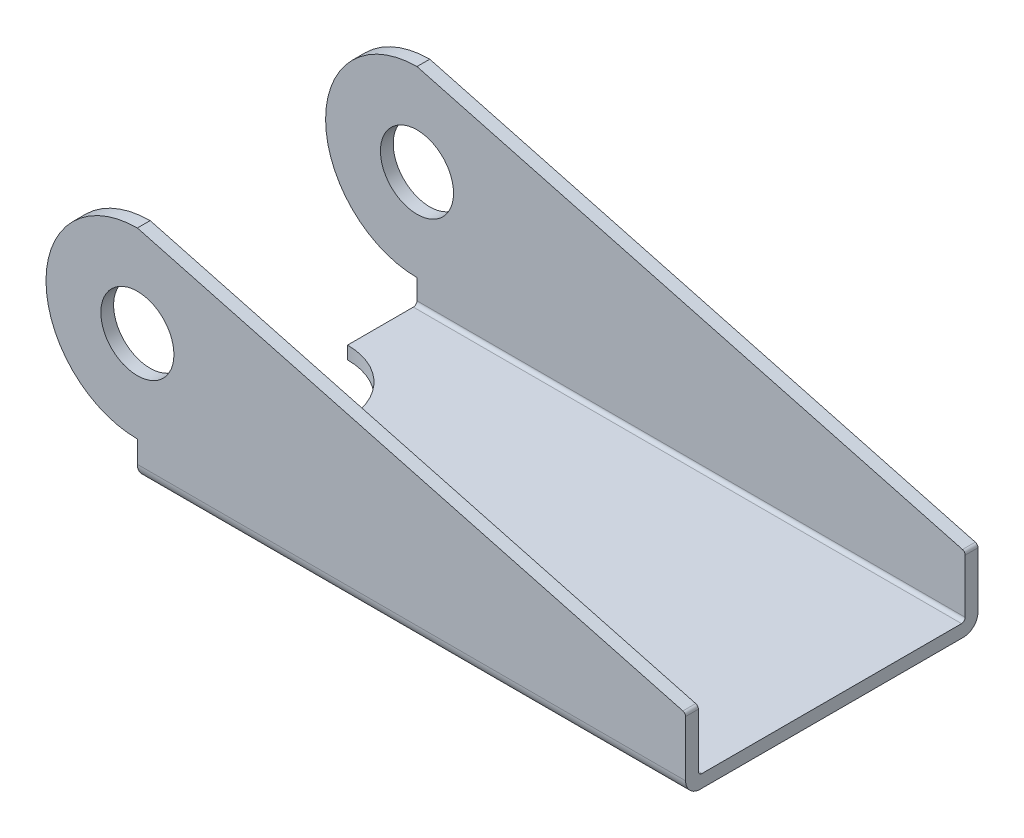
SolidWorks part; units mm, degrees
ref_plane "Front Plane" through (0, 0, 0) normal (0, 0, 1) x (1, 0, 0)
ref_plane "Top Plane" through (0, 0, 0) normal (0, 1, 0) x (1, 0, 0)
ref_plane "Right Plane" through (0, 0, 0) normal (1, 0, 0) x (0, 0, -1)
sketch "Sketch2" plane through (0, 0, 0) normal (0, 0, 1) x (1, 0, 0)
  line L0 (-19.05, 0) -> (19.05, 0)
  line L1 (19.05, 0) -> (19.05, 5.08)
  line L2 (19.05, 5.08) -> (-19.05, 15.24)
  line L3 (-19.05, 0) -> (-19.05, 2.54)
  line L4 (55, 0) -> (-55, 0) construction
  arc A0 (-19.05, 2.54) -> (-19.05, 15.24) centre (-19.05, 8.89) cw
  point P8 (0, 0)
  dimension "D1" = 38.1
  dimension "D2" = 5.08
  dimension "D3" = 15.24
  dimension "D4" = 6.35
extrude "Extruded Boss Front Plane Wing" add sketch "Sketch2" along normal blind 10.16 and the other way blind 10.16
sketch "Sketch3" plane through (0, 0, 0) normal (1, 0, 0) x (0, 0, -1)
  line L0 (-9.271, 15.24) -> (-9.271, 0.889)
  line L1 (10.16, 15.24) -> (-10.16, 15.24) construction
  line L2 (-9.271, 0.889) -> (9.271, 0.889)
  line L3 (9.271, 0.889) -> (9.271, 15.24)
  line L4 (9.271, 15.24) -> (-9.271, 15.24)
  line L5 (-10.16, 0) -> (-10.16, 5.08) construction
  line L6 (10.16, 0) -> (10.16, 5.08) construction
  line L7 (55, 0) -> (-55, 0) construction
  dimension "D1" = 0.889
  dimension "D2" = 0.889
  dimension "D3" = 0.889
extrude "Extruded Cut Right Plane Wing" cut sketch "Sketch3" against normal through all and the other way through all
hole_wizard "2X 0.2D Holes" positions "Sketch4" profile "Sketch5" hole size "1/16" standard "ANSI Inch" end condition through all
sketch "Sketch4" plane through (0, 0, 10.16) normal (0, 0, 1) x (1, 0, 0)
  point P0 (-19.05, 8.89)
sketch "Sketch5" plane through (-19.05, 8.89, 10.16) normal (1, 0, 0) x (0, -1, 0)
  line L0 (0, 0) -> (0, 20.32)
  line L1 (0, 20.32) -> (2.54, 20.32)
  line L2 (2.54, 20.32) -> (2.54, 0)
  line L5 (2.54, 0) -> (0, 0)
  line L11 (0, -6.35) -> (0, 107.95) construction
  dimension "Thru Hole Dia." = 5.08
  dimension "Thru Hole Depth" = 20.32
hole_wizard "0.35D Hole" positions "Sketch6" profile "Sketch7" hole size "1/16" standard "ANSI Inch" end condition through all
sketch "Sketch6" plane through (0, 0.889, 0) normal (0, 1, 0) x (1, 0, 0)
  line L0 (-19.05, 9.271) -> (-19.05, -9.271) construction
  point P0 (-19.05, 0)
sketch "Sketch7" plane through (-19.05, 0.889, 0) normal (1, 0, 0) x (0, 0, 1)
  line L0 (0, 0) -> (0, 0.889)
  line L1 (0, 0.889) -> (4.445, 0.889)
  line L2 (4.445, 0.889) -> (4.445, 0)
  line L5 (4.445, 0) -> (0, 0)
  line L11 (0, -6.35) -> (0, 107.95) construction
  dimension "Thru Hole Dia." = 8.89
  dimension "Thru Hole Depth" = 0.889
fillet "Inner Connecting Fillet" radius 0.254 4 edges at (0, 0.889, 9.271) (0, 0.889, -9.271) (19.05, 5.08, -9.7155) (19.05, 5.08, 9.7155)
fillet "Outter Connecting Fillet" radius 1.016 2 edges at (0, 0, -10.16) (0, 0, 10.16)
